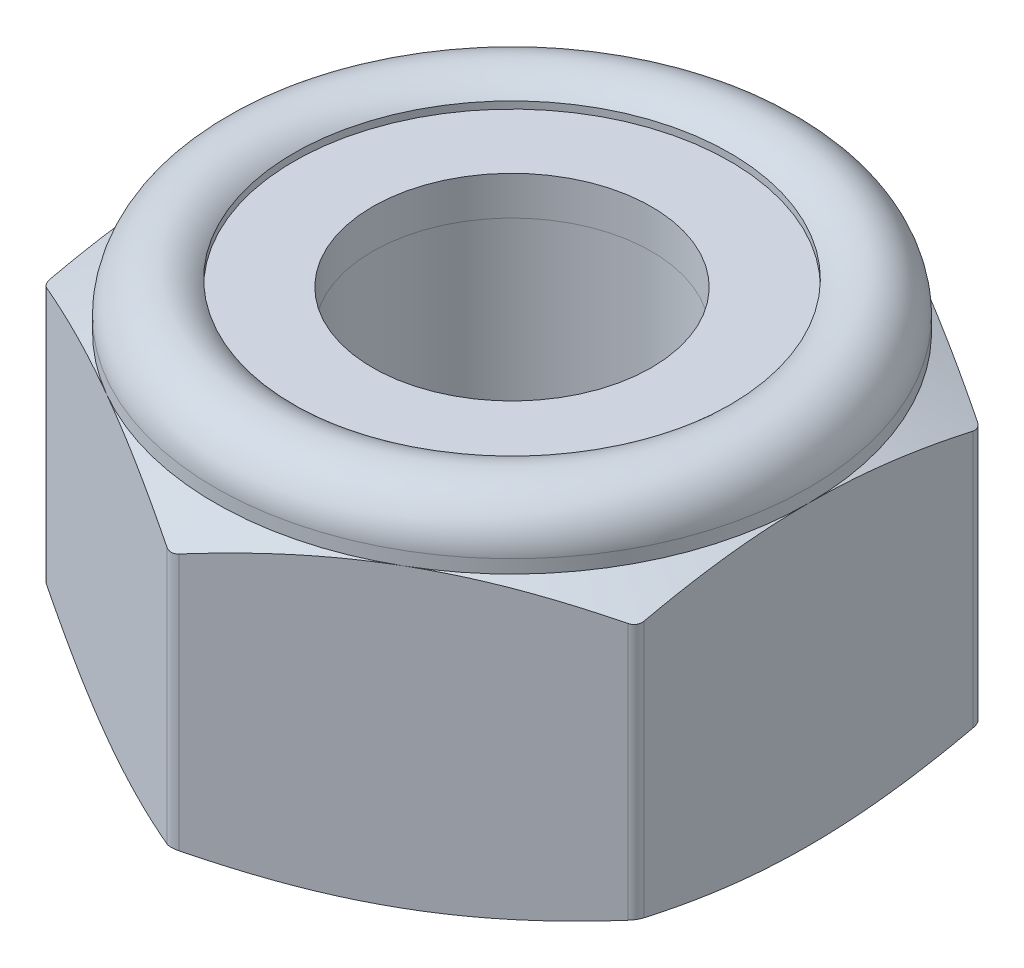
SolidWorks part; units mm, degrees
material "Alloy Steel"
ref_plane "Front Plane" through (0, 0, 0) normal (0, 0, 1) x (1, 0, 0)
ref_plane "Top Plane" through (0, 0, 0) normal (0, 1, 0) x (1, 0, 0)
ref_plane "Right Plane" through (0, 0, 0) normal (1, 0, 0) x (0, 0, -1)
sketch "Sketch1" plane through (0, 0, 0) normal (0, 0, 1) x (1, 0, 0)
  line L0 (0, -3) -> (0, 3) construction
  line L1 (5, 0) -> (-5, 0) construction
  line L2 (3, -3) -> (-3, -3) construction
  line L3 (3, -3) -> (3, -2) construction
  point P4 (0, 0)
  point P8 (0, 0)
  point P11 (0, -3)
  dimension "Height" = 6
  dimension "Width" = 10
  dimension "Thread Size" = 6
  dimension "Thread Pitch" = 1
sketch "Sketch2" plane through (0, 0, 0) normal (0, 1, 0) x (1, 0, 0)
  line L0 (-3, 0.4375) -> (-3, -0.4375) construction
  line L1 (0, 5.7735) -> (-5, 2.8868)
  line L2 (-5, 2.8868) -> (-5, -2.8868)
  line L3 (-5, -2.8868) -> (0, -5.7735)
  line L4 (0, -5.7735) -> (5, -2.8868)
  line L5 (5, -2.8868) -> (5, 2.8868)
  line L6 (5, 2.8868) -> (0, 5.7735)
  line L7 (-3, -0.4375) -> (-2.3505, -0.0625) construction
  line L8 (-2.3505, -0.0625) -> (-2.3505, 0.0625) construction
  line L9 (-2.3505, 0.0625) -> (-3, 0.4375) construction
  line L10 (-2.3505, 0) -> (-3, 0) construction
  line L11 (-2.6752, 0.25) -> (-2.6752, -0.25) construction
  line L12 (3, 0) -> (-3, 0) construction
  line L13 (5, 0) -> (-5, 0) construction
  circle A0 centre (0, 0) radius 5 construction
  circle A1 centre (0, 0) radius 2.3505
  point P19 (0, -2.3505)
  dimension "D1" = 0.125
  dimension "D2" = 0.5
  dimension "D3" = 60
extrude "Boss-Extrude1" add sketch "Sketch2" along normal up to vertex (3 mm away) and the other way up to vertex (3 mm away) up to point (0, 3, 0) other way up to point (0, -3, 0)
fillet "Fillet1" radius 0.2 6 edges at (-5, 0, -2.8868) (0, 0, -5.7735) (-5, 0, 2.8868) (5, 0, -2.8868) (5, 0, 2.8868) (0, 0, 5.7735)
sketch "Sketch3" plane through (0, 0, 0) normal (1, 0, 0) x (0, 0, -1)
  line L0 (5.7735, 2) -> (5.7735, 4)
  line L2 (5, -3) -> (5.7735, -2.6393)
  line L3 (2.9445, -3) -> (5.7158, -3) construction
  line L4 (5.7735, 3) -> (5.7735, -3) construction
  line L5 (5.7735, -2.6393) -> (5.7735, -3)
  line L6 (5.7735, -3) -> (5, -3)
  line L7 (5, 2) -> (5.7735, 1.6393)
  line L8 (5.7735, 1.6393) -> (5.7735, 2)
  line L11 (5, 2) -> (5, 2.224)
  line L12 (2.9445, 3) -> (5.7158, 3) construction
  line L13 (2.3505, 2) -> (3.6752, 2)
  line L14 (3.6752, 2) -> (3.6752, 2.7727)
  line L15 (3.6752, 2) -> (5, 2) construction
  line L16 (3.6752, 2.7727) -> (4.224, 2.224) construction
  line L17 (4.224, 2.224) -> (4.224, 3) construction
  line L18 (2.3505, 2) -> (2.3505, 4)
  line L19 (2.3505, 4) -> (5.7735, 4)
  line L21 (2.3505, -3) -> (2.3505, -2.4)
  line L22 (-2.7713, -3) -> (2.7713, -3) construction
  line L24 (2.9505, -3) -> (2.3505, -3)
  line L25 (2.3505, -2.4) -> (2.9505, -3)
  arc A0 (5, 2.224) -> (3.6752, 2.7727) centre (4.224, 2.224) ccw
  point P0 (5, 2)
  point P1 (5, 0)
  point P14 (2.3505, 0)
  dimension "D1" = 5
  dimension "D2" = 25
  dimension "D3" = 45
  dimension "D4" = 1
  dimension "D5" = 0.6
revolve "Cut-Revolve2" cut sketch "Sketch3" angle 360 about L0
sketch "Sketch4" plane through (0, 0, 0) normal (1, 0, 0) x (0, 0, -1)
  line L0 (-3.6752, 2.7727) -> (-3.6752, 2) construction
  line L1 (-2.3505, 2) -> (-3.6752, 2)
  line L2 (-2.3505, 2) -> (-2.3505, 2.6527)
  line L3 (-2.3505, 2.6527) -> (-3.6752, 2.6527)
  line L4 (-3.6752, 2) -> (-3.6752, 2.6527)
  line L5 (3.6752, 2.7727) -> (-3.6752, 2.7727) construction
  line L6 (2.3505, 2) -> (-2.3505, 2) construction
  dimension "D1" = 0.12
revolve "Revolve1" add sketch "Sketch4" angle 360 about L0
sketch "Sketch5" plane through (0, 0, 0) normal (0, 1, 0) x (1, 0, 0)
  circle A0 centre (0, 0) radius 2.3505 construction
  point P0 (0, -2.3505)
sketch "Sketch6" [suppressed] plane through (0, 0, 0) normal (0, 0, 1) x (1, 0, 0)
  line L0 (3, 2) -> (3, -3)
  line L2 (0, -3) -> (5, -3) construction
  line L3 (3, -3) -> (0, -3)
  line L4 (0, -3) -> (0, 2)
  line L5 (0, -3) -> (0, 3) construction
  line L6 (0, 2) -> (3, 2)
  line L7 (5, 2) -> (2.5, 2) construction
revolve "Revolve2" [suppressed] add sketch "Sketch6" angle 360 about L4
sketch "Sketch7" [suppressed] plane through (0, -3, 0) normal (0, -1, 0) x (1, 0, 0)
  circle A2 centre (0, 0) radius 3
  circle A3 centre (0, 0) radius 3
  dimension "D1" = 0
curve "Helix/Spiral1" [suppressed] pitch 1 height 6 turns 6
sketch "Sketch8" [suppressed] plane through (0, 0, 0) normal (0, 0, 1) x (1, 0, 0)
  line L0 (3.1083, -2.9375) -> (2.2422, -3.4375) construction
  line L1 (2.2422, -3.4375) -> (3.1083, -3.9375) construction
  line L2 (3.1083, -3.9375) -> (3.1083, -2.9375) construction
  line L3 (2.3505, -3.375) -> (2.3505, -3.5)
  line L4 (3, -3) -> (3, -3.875) construction
  line L5 (3, -3.4375) -> (3.1083, -3.4375) construction
  line L6 (2.2422, -3.4375) -> (2.3505, -3.4375) construction
  line L7 (3.0541, -3.4375) -> (3.0541, -3.9062) construction
  line L8 (2.3505, -3.375) -> (3.1083, -2.9375)
  line L9 (3.1083, -2.9375) -> (3.0541, -3.9062)
  line L10 (2.3505, -3.5) -> (3.0541, -3.9062)
  dimension "D1" = 1
  dimension "D2" = 0.125
sweep "Cut-Sweep1" [suppressed] cut profiles "Sketch8" path "Helix/Spiral1"
sketch "Sketch9" [suppressed] plane through (0, 0, 0) normal (0, 0, 1) x (1, 0, 0)
  line L0 (0, 0) -> (0, -3)
  line L1 (0, 0) -> (0, 0.6)
  line L2 (0, -3) -> (3, -3)
  line L3 (3, -3) -> (3.6, -3)
  line L4 (3.6, -3) -> (0, 0.6)
  dimension "D1" = 0.6
revolve "Revolve3" [suppressed] add sketch "Sketch9" angle 360 about L0
sketch "Sketch10" [suppressed] plane through (0, -3, 0) normal (0, -1, 0) x (1, 0, 0)
  circle A0 centre (0, 0) radius 2.9505 construction
  circle A1 centre (0, 0) radius 2.9505
extrude "Boss-Extrude2" [suppressed] add sketch "Sketch10" against normal up to surface (5 mm away) up to face at (3.6752, 2, 0)
combine bodies "Combine1" [suppressed] operation type add bodies to combine 110 109
equation "\"D1@Sketch3\"=\"Height@sketch1\"*(5/6)"
equation "\"D5@Sketch3\"=\"Thread Size@Sketch1\"*.1"
equation "\"D4@Helix/Spiral1\"=\"Thread Pitch@sketch1\""
equation "\"D3@Helix/Spiral1\"=\"Height@sketch1\""
equation "\"D1@Sketch8\"=\"Thread Pitch@sketch1\""
equation "\"D2@Sketch8\"=\"Thread Pitch@sketch1\"/8"
equation "\"D1@Sketch9\"=\"Thread Size@Sketch1\" * .1"
equation "\"D1@Sketch2\"=\"Thread Pitch@sketch1\"/8"
equation "\"D2@Sketch2\"=\"Thread Pitch@sketch1\"/2"
equation "\"D1@Sketch4\" = \"Height@Sketch1\" * .02"
equation "\"D1@Fillet1\"=\"Width@sketch1\"*.02"
